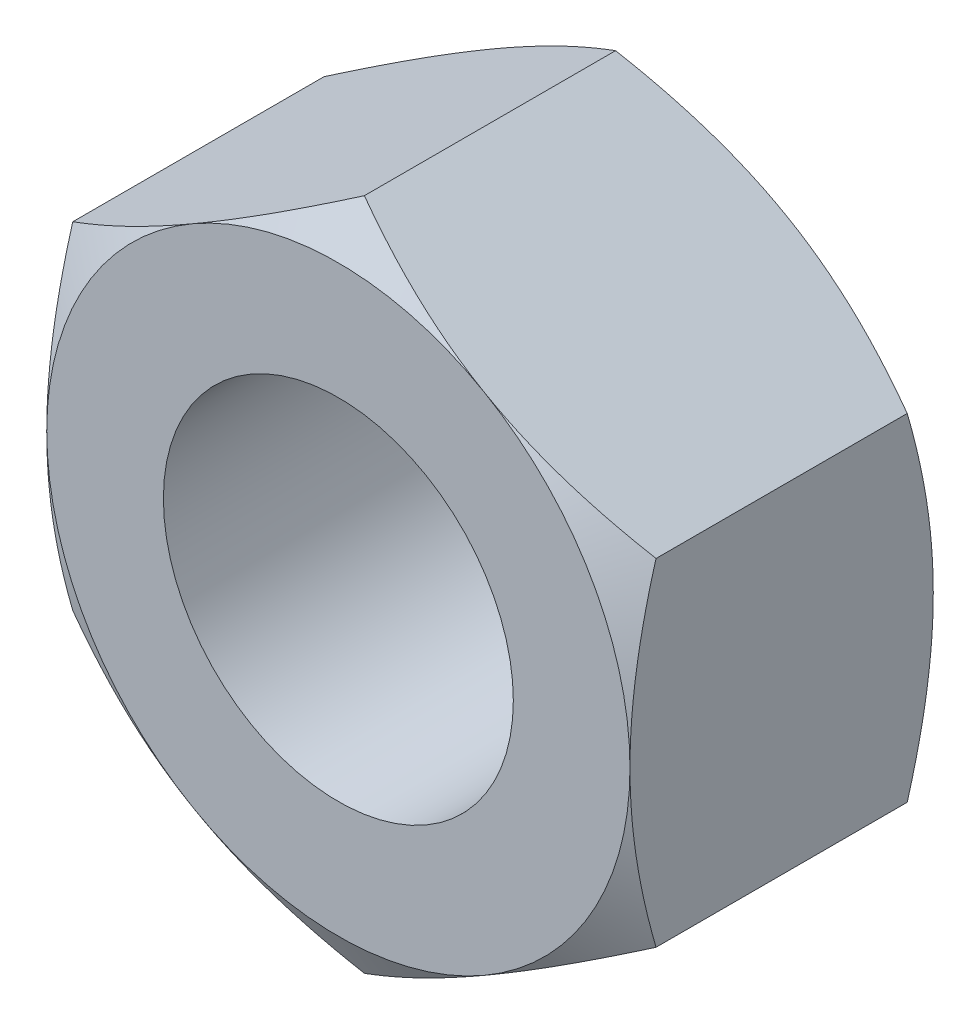
SolidWorks part; units mm, degrees
material "AISI 4340 Steel, normalized"
ref_plane "Front Plane" through (0, 0, 0) normal (0, 0, 1) x (1, 0, 0)
ref_plane "Top Plane" through (0, 0, 0) normal (0, 1, 0) x (1, 0, 0)
ref_plane "Right Plane" through (0, 0, 0) normal (1, 0, 0) x (0, 0, -1)
sketch "Sketch1" plane through (0, 0, 0) normal (1, 0, 0) x (0, 0, -1)
  line L0 (-2.6, 0) -> (2.6, 0) construction
  line L1 (-2.6, -5) -> (-2.6, 5) construction
  line L2 (2.6, -5) -> (2.6, 5) construction
  line L3 (-2.6, -3) -> (-2.6, 3) construction
  line L4 (-3.5375, 3.1083) -> (-3.0375, 2.2422) construction
  line L5 (-3.0375, 2.2422) -> (-2.5375, 3.1083) construction
  line L6 (-2.5375, 3.1083) -> (-3.5375, 3.1083) construction
  line L7 (-3.5063, 3.0541) -> (-2.5688, 3.0541) construction
  line L8 (-3.475, 3) -> (-2.6, 3) construction
  line L9 (-3.1, 2.3505) -> (-2.975, 2.3505) construction
  line L10 (-3.0375, 2.3505) -> (-3.0375, 2.2422) construction
  line L11 (-3.0375, 3.1083) -> (-3.0375, 3) construction
  point P4 (0, 0)
  point P7 (-2.6, 0)
  point P11 (2.6, 0)
  point P14 (-2.6, 0)
  point P26 (-3.0375, 3.0541)
  point P27 (-2.6, -3)
  dimension "Height" = 5.2
  dimension "Width" = 10
  dimension "Thread OD" = 6
  dimension "D1" = 60
  dimension "Pitch" = 1
  dimension "D2" = 0.125
sketch "Sketch2" plane through (0, 0, 0) normal (0, 0, 1) x (1, 0, 0)
  line L1 (0, 5.7735) -> (-5, 2.8868)
  line L2 (-5, 2.8868) -> (-5, -2.8868)
  line L3 (-5, -2.8868) -> (0, -5.7735)
  line L4 (0, -5.7735) -> (5, -2.8868)
  line L5 (5, -2.8868) -> (5, 2.8868)
  line L6 (5, 2.8868) -> (0, 5.7735)
  circle A0 centre (0, 0) radius 5 construction
  circle A1 centre (0, 0) radius 3
extrude "Boss-Extrude1" add sketch "Sketch2" along normal up to vertex (2.6 mm away) and the other way up to vertex (2.6 mm away) up to point (0, -5, 2.6) other way up to point (0, -5, -2.6)
sketch "Sketch3" plane through (0, 0, 2.6) normal (0, 0, 1) x (1, 0, 0)
  circle A0 centre (0, 0) radius 5
extrude "Cut-Extrude1" cut sketch "Sketch3" against normal through all draft 60 flip side to cut
mirror "Mirror1" about plane through (0, 0, 0) normal (0, 0, 1) of "Cut-Extrude1"
ref_axis "Center Axis 1" through (0, 0, -1.0465) along (0, 0, 1)
ref_plane "Contact Plane 1" through (0, 0, 2.6) normal (0, 0, 1) x (1, 0, 0)
ref_plane "Contact Plane 2" through (0, 0, -2.6) normal (0, 0, -1) x (-1, 0, 0)
sketch "Sketch4" plane through (0, 0, 0) normal (1, 0, 0) x (0, 0, -1)
  line L0 (-2.6, 3) -> (-3.475, 3)
  line L1 (-3.475, 3) -> (-3.1, 2.3505)
  line L2 (-3.1, 2.3505) -> (-2.975, 2.3505)
  line L3 (-2.975, 2.3505) -> (-2.6, 3)
sketch "Sketch5" plane through (0, 0, 2.6) normal (0, 0, 1) x (1, 0, 0)
  circle A0 centre (0, 0) radius 3 construction
  circle A1 centre (0, 0) radius 3
sketch "Sketch6" plane through (0, 0, 2.6) normal (0, 0, 1) x (1, 0, 0)
  circle A0 centre (0, 0) radius 3 construction
  circle A1 centre (0, 0) radius 3
equation "\"D2@Sketch1\"=\"Pitch@Sketch1\"/8"
